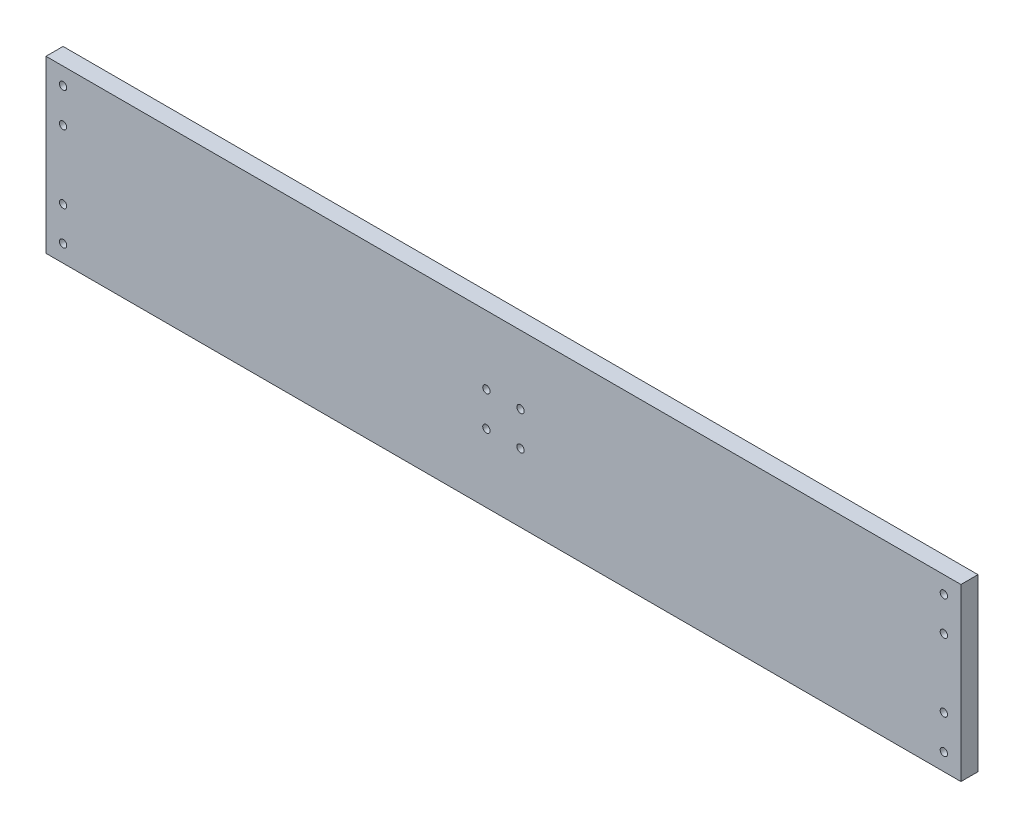
SolidWorks part; units mm, degrees
ref_plane "Piano frontale" through (0, 0, 0) normal (0, 0, 1) x (1, 0, 0)
ref_plane "Piano superiore" through (0, 0, 0) normal (0, 1, 0) x (1, 0, 0)
ref_plane "Piano destro" through (0, 0, 0) normal (1, 0, 0) x (0, 0, -1)
sketch "Schizzo1" plane through (0, 0, 0) normal (0, 0, 1) x (1, 0, 0)
  line L0 (10, 100) -> (10, 0) construction
  line L1 (0, 0) -> (536, 0)
  line L2 (0, 0) -> (0, 100)
  line L3 (0, 100) -> (536, 100)
  line L4 (536, 0) -> (536, 100)
  line L5 (0, 50) -> (10.4526, 50) construction
  line L6 (268, 100) -> (268, 0) construction
  line L7 (536, 50) -> (525.5474, 50) construction
  line L8 (526, 100) -> (526, 0) construction
  circle A0 centre (10, 90) radius 2.15
  circle A1 centre (10, 70) radius 2.15
  circle A2 centre (10, 30) radius 2.15
  circle A3 centre (526, 10) radius 2.15
  circle A4 centre (526, 30) radius 2.15
  circle A5 centre (526, 70) radius 2.15
  circle A6 centre (10, 10) radius 2.15
  circle A7 centre (526, 90) radius 2.15
  dimension "D4" = 4.3
  dimension "D5" = 10
  dimension "D1" = 100
  dimension "D2" = 536
  dimension "D3" = 40
  dimension "D6" = 20
extrude "Estrusione-Estrusione1" add sketch "Schizzo1" against normal blind 10
sketch "Schizzo2" plane through (0, 0, 0) normal (0, 0, 1) x (1, 0, 0)
  line L0 (268, 100) -> (268, 0) construction
  line L1 (536, 100) -> (0, 100) construction
  line L2 (0, 50) -> (536, 50) construction
  line L3 (0, 0) -> (536, 0) construction
  line L4 (285, 50) -> (265, 50) construction
  line L9 (0, 100) -> (0, 0) construction
  line L10 (536, 0) -> (536, 100) construction
  circle A0 centre (258, 60) radius 2.15
  circle A1 centre (278, 60) radius 2.15
  circle A4 centre (278, 40) radius 2.15
  circle A5 centre (258, 40) radius 2.15
  dimension "D3" = 4.3
  dimension "D1" = 10
  dimension "D2" = 10
  dimension "D4" = 10
extrude "Taglio-Estrusione1" cut sketch "Schizzo2" against normal through all
